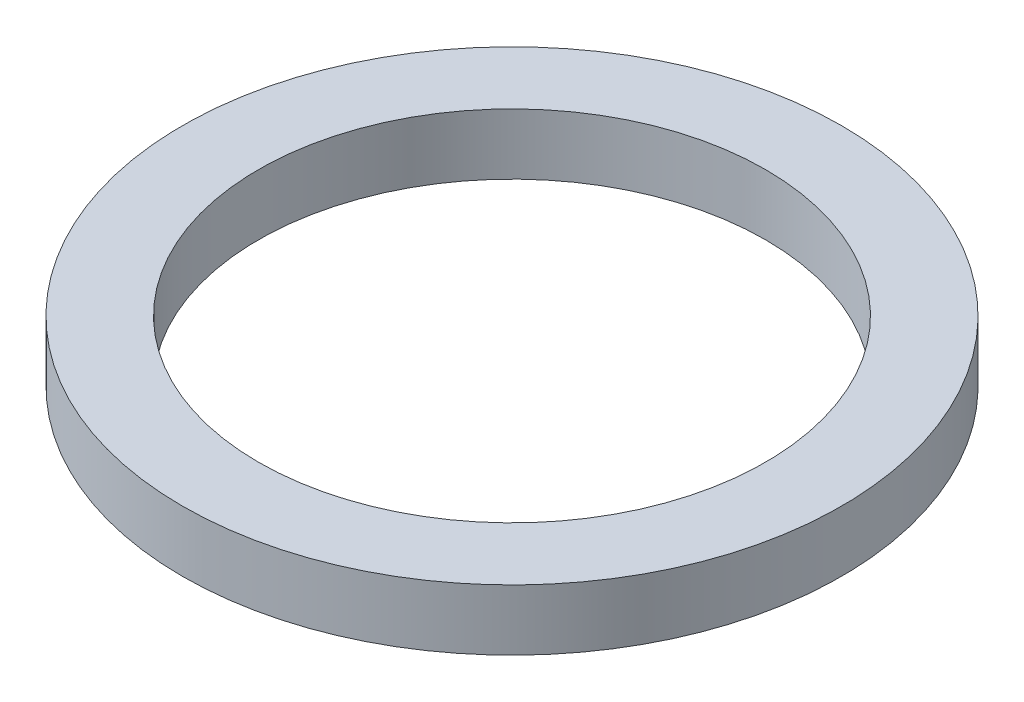
SolidWorks part; units mm, degrees
ref_plane "Front Plane" through (0, 0, 0) normal (0, 0, 1) x (1, 0, 0)
ref_plane "Top Plane" through (0, 0, 0) normal (0, 1, 0) x (1, 0, 0)
ref_plane "Right Plane" through (0, 0, 0) normal (1, 0, 0) x (0, 0, -1)
sketch "Sketch1" plane through (0, 0, 0) normal (0, 1, 0) x (1, 0, 0)
  circle A0 centre (0, 0) radius 65
  dimension "FLANGE_OD" = 130
extrude "Boss-Extrude1" add sketch "Sketch1" along normal blind 12
sketch "Sketch2" plane through (0, 0, 0) normal (0, 1, 0) x (1, 0, 0)
  circle A0 centre (0, 0) radius 50
  dimension "BORE_D" = 100
extrude "Cut-Extrude1" cut sketch "Sketch2" along normal through all
sketch "Sketch3" plane through (0, 12, 0) normal (0, 1, 0) x (1, 0, 0)
  circle A0 centre (0, 0) radius 27.6129 construction
  circle A1 centre (-27.6129, 0) radius 2.2251
  dimension "BOLT_D" = 4.4503
  dimension "BOLT_PCD" = 55.2258
extrude "Cut-Extrude2" cut sketch "Sketch3" against normal blind 9.954 rebuild error yes
pattern_circular "CirPattern1" count 3 over 360 rebuild error yes
